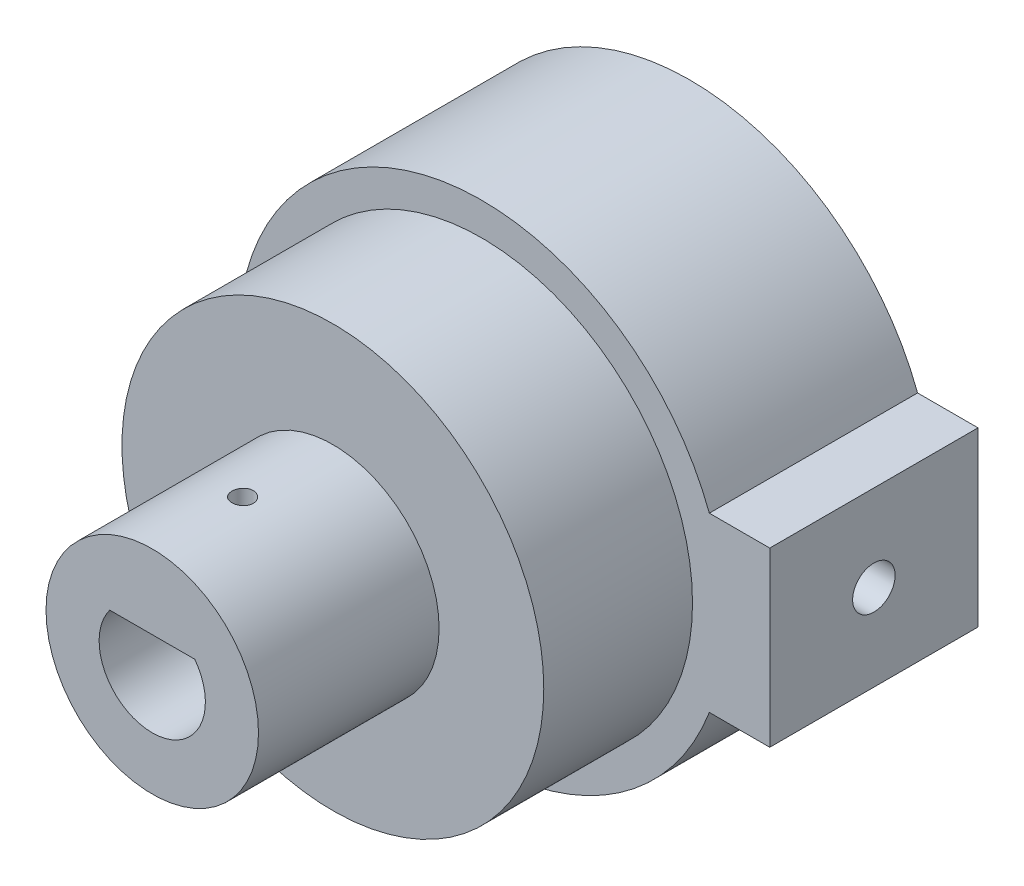
SolidWorks part; units mm, degrees
ref_plane "Front Plane" through (0, 0, 0) normal (0, 0, 1) x (1, 0, 0)
ref_plane "Top Plane" through (0, 0, 0) normal (0, 1, 0) x (1, 0, 0)
ref_plane "Right Plane" through (0, 0, 0) normal (1, 0, 0) x (0, 0, -1)
sketch "Sketch1" plane through (0, 0, 0) normal (0, 0, 1) x (1, 0, 0)
  line L0 (-11.46, 0) -> (11.46, 0) construction
  line L1 (11.46, 0) -> (17.06, 0) construction
  line L2 (-6.75, -6.75) -> (6.75, -6.75)
  line L3 (-6.75, -6.75) -> (-6.75, 6.75)
  line L4 (-6.75, 6.75) -> (6.75, 6.75)
  line L5 (6.75, -6.75) -> (6.75, 6.75)
  line L6 (-6.75, -6.75) -> (6.75, 6.75) construction
  line L7 (-6.75, 6.75) -> (6.75, -6.75) construction
  line L9 (10.7167, 4.06) -> (17.06, 4.06)
  line L11 (10.7167, -4.06) -> (17.06, -4.06)
  line L12 (17.06, 4.06) -> (17.06, -4.06)
  arc A0 (10.7167, 4.06) -> (10.7167, -4.06) centre (0, 0) ccw
  arc A1 (-6.75, 5.1495) -> (-6.75, -5.1495) centre (0, 0) ccw
  arc A2 (-5.1495, -6.75) -> (5.1495, -6.75) centre (0, 0) ccw
  arc A3 (5.1495, 6.75) -> (-5.1495, 6.75) centre (0, 0) ccw
  arc A4 (6.75, -5.1495) -> (6.75, 5.1495) centre (0, 0) ccw
  point P15 (17.06, 0)
  dimension "D1" = 22.92
  dimension "D2" = 2.97
  dimension "D3" = 13.5
  dimension "D4" = 5.6
  dimension "D5" = 8.12
  dimension "D6" = 6.3433
extrude "Boss-Extrude1" add sketch "Sketch1" along normal blind 9.8 contours L9 A0 L11 L12 A4 L5 L2 A2 L3 A1 L4 A3 | L4 A3 | L3 A1 | L5 A4 | L2 A2 region at (0, -7.4525, 0) region at (-7.4525, 0, 0) region at (7.4525, 0, 0) region at (0, 7.4525, 0) region at (13.8884, 3.6941, 0)
sketch "Sketch2" plane through (0, 0, 9.8) normal (0, 0, 1) x (1, 0, 0)
  circle A0 centre (0, 0) radius 9.925
  dimension "D1" = 19.85
extrude "Boss-Extrude2" add sketch "Sketch2" along normal blind 7
sketch "Sketch3" plane through (0, 0, 9.8) normal (0, 0, -1) x (-1, 0, 0)
  line L0 (6.75, 6.75) -> (-6.75, 6.75) construction
  line L1 (-6.75, -6.75) -> (6.75, -6.75)
  line L2 (-6.75, -6.75) -> (-6.75, 6.75)
  line L3 (-6.75, 6.75) -> (6.75, 6.75)
  line L4 (6.75, -6.75) -> (6.75, 6.75)
  line L5 (-6.75, -6.75) -> (6.75, 6.75) construction
  line L6 (-6.75, 6.75) -> (6.75, -6.75) construction
  line L7 (6.75, -6.75) -> (6.75, 6.75) construction
  point P0 (0, 0)
extrude "Cut-Extrude1" cut sketch "Sketch3" against normal blind 5
sketch "Sketch4" plane through (0, 0, 16.8) normal (0, 0, 1) x (1, 0, 0)
  line L0 (0, 2.5) -> (0, 1.5) construction
  line L1 (2, 1.5) -> (-2, 1.5)
  circle A0 centre (0, 0) radius 5
  arc A1 (-2, 1.5) -> (2, 1.5) centre (0, 0) ccw
  dimension "D1" = 10
  dimension "D2" = 5
  dimension "D3" = 1
  dimension "D4" = 4
extrude "Boss-Extrude3" add sketch "Sketch4" along normal blind 8.5
sketch "Sketch5" plane through (17.06, 0, 0) normal (1, 0, 0) x (0, 0, -1)
  line L0 (0, 0) -> (-9.8, 0) construction
  line L1 (-9.8, 4.06) -> (-9.8, -4.06) construction
  circle A0 centre (-4.9, 0) radius 1
  dimension "D1" = 2
extrude "Cut-Extrude2" cut sketch "Sketch5" against normal blind 10.5
sketch "Sketch6" plane through (0, 1.5, 0) normal (0, -1, 0) x (1, 0, 0)
  line L0 (0, 25.3) -> (0, 16.8) construction
  line L1 (5, 25.3) -> (-5, 25.3) construction
  line L2 (9.925, 16.8) -> (-9.925, 16.8) construction
  circle A0 centre (0, 21.05) radius 0.5
  dimension "D1" = 1
extrude "Cut-Extrude3" cut sketch "Sketch6" against normal blind 3.5
sketch "Sketch7" plane through (0, 0, 0) normal (0, 0, -1) x (-1, 0, 0)
  line L1 (-17.06, 4.06) -> (-17.06, -4.06) construction
  line L2 (-17.06, 0) -> (-6.75, 0) construction
  line L3 (-6.75, 6.75) -> (-6.75, -6.75) construction
  line L4 (-10.7167, -4.06) -> (-17.06, -4.06) construction
  line L5 (-17.06, 4.06) -> (-13.56, 4.06)
  line L6 (-17.06, 4.06) -> (-17.06, -4.06)
  line L7 (-17.06, -4.06) -> (-13.56, -4.06)
  line L8 (-13.56, 4.06) -> (-13.56, -4.06)
  dimension "D1" = 3.5
extrude "Cut-Extrude4" cut sketch "Sketch7" against normal blind 10.5
